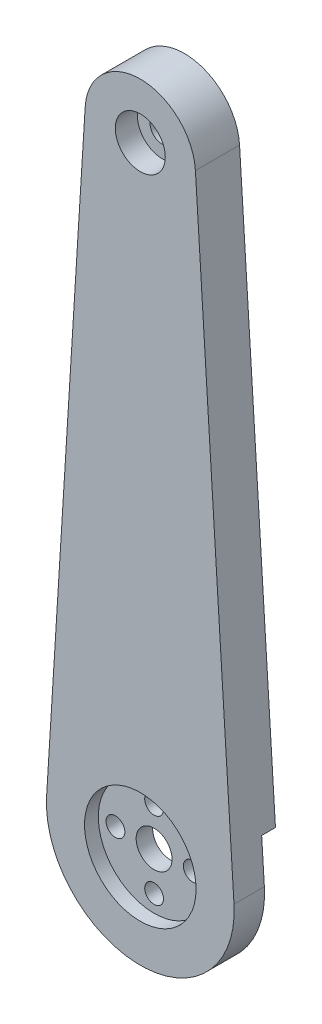
SolidWorks part; units mm, degrees
ref_plane "Front Plane" through (0, 0, 0) normal (0, 0, 1) x (1, 0, 0)
ref_plane "Top Plane" through (0, 0, 0) normal (0, 1, 0) x (1, 0, 0)
ref_plane "Right Plane" through (0, 0, 0) normal (1, 0, 0) x (0, 0, -1)
sketch "Sketch1" plane through (0, 0, 0) normal (0, 0, 1) x (1, 0, 0)
  line L0 (16.967, 1.062) -> (9.98, 112.625)
  line L1 (-9.98, 112.625) -> (-16.967, 1.062)
  arc A0 (9.98, 112.625) -> (-9.98, 112.625) centre (0, 112) ccw
  arc A1 (-16.967, 1.062) -> (16.967, 1.062) centre (0, 0) ccw
  circle A2 centre (0, 0) radius 3.25
  circle A3 centre (7, 0) radius 1.7
  circle A4 centre (0, 7) radius 1.7
  circle A5 centre (-7, 0) radius 1.7
  circle A6 centre (0, -7) radius 1.7
  circle A7 centre (0, 112) radius 2.25
extrude "Boss-Extrude1" add sketch "Sketch1" along normal blind 8
sketch "Sketch2" plane through (0, 0, 8) normal (0, 0, 1) x (1, 0, 0)
  circle A0 centre (0, 0) radius 10.1
extrude "Cut-Extrude1" cut sketch "Sketch2" against normal blind 2.5
sketch "Sketch3" plane through (0, 0, 8) normal (0, 0, 1) x (1, 0, 0)
  circle A0 centre (0, 112) radius 4.525
extrude "Cut-Extrude2" cut sketch "Sketch3" against normal blind 4
sketch "Sketch4" plane through (0, 0, 0) normal (0, 0, 1) x (1, 0, 0)
  line L0 (13.45, 13) -> (7.7, 103)
  line L1 (-7.7, 103) -> (-13.45, 13)
  arc A0 (7.7, 103) -> (-7.7, 103) centre (0, 112) cw
  arc A1 (-13.45, 13) -> (13.45, 13) centre (0, 0) ccw
extrude "Cut-Extrude3" cut sketch "Sketch4" along normal blind 2.5
